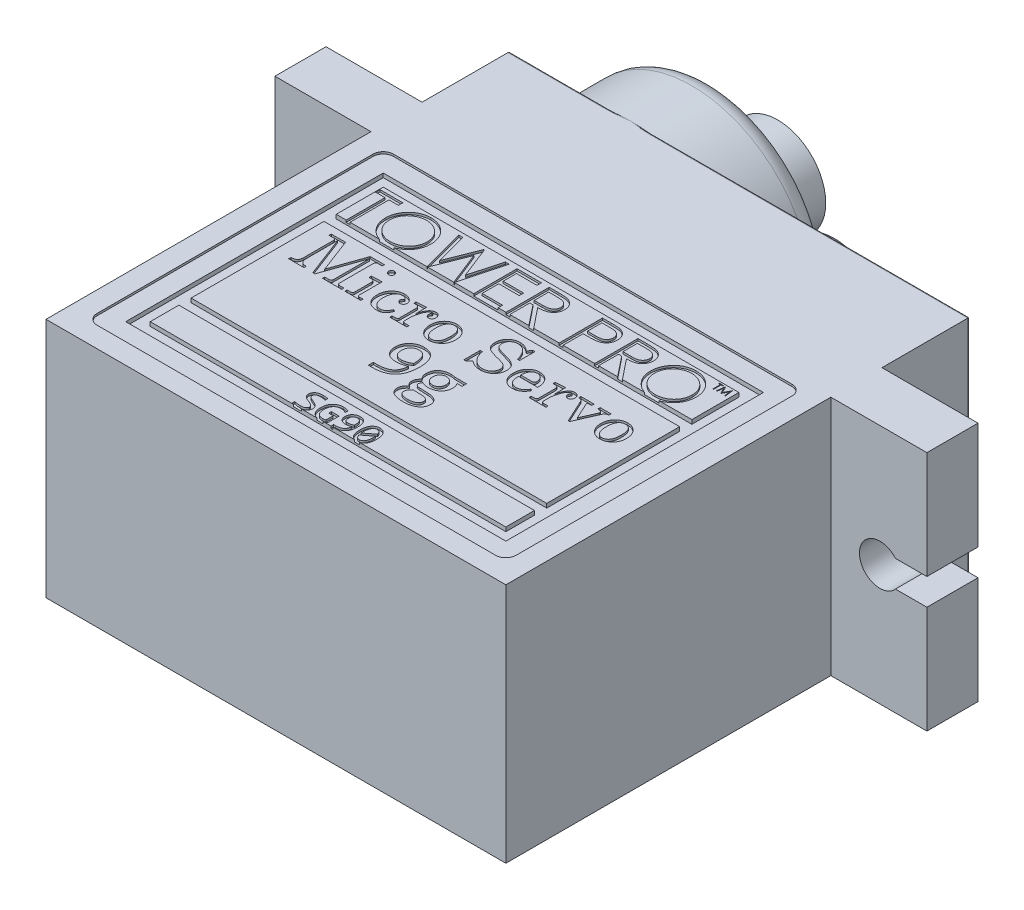
SolidWorks part; units mm, degrees
ref_plane "Front Plane" through (0, 0, 0) normal (0, 0, 1) x (1, 0, 0)
ref_plane "Top Plane" through (0, 0, 0) normal (0, 1, 0) x (1, 0, 0)
ref_plane "Right Plane" through (0, 0, 0) normal (1, 0, 0) x (0, 0, -1)
sketch "Sketch1" plane through (0, 0, 0) normal (0, 1, 0) x (1, 0, 0)
  line L1 (-11.25, -11.35) -> (11.25, -11.35)
  line L2 (-11.25, -11.35) -> (-11.25, 11.35)
  line L3 (-11.25, 11.35) -> (11.25, 11.35)
  line L4 (11.25, -11.35) -> (11.25, 11.35)
  line L5 (-11.25, -11.35) -> (11.25, 11.35) construction
  line L6 (-11.25, 11.35) -> (11.25, -11.35) construction
  point P0 (0, 0)
  dimension "D1" = 22.5
  dimension "D2" = 22.7
extrude "Boss-Extrude1" add sketch "Sketch1" along normal mid plane 11.8
sketch "Sketch2" plane through (11.25, 0, 0) normal (1, 0, 0) x (0, 0, -1)
  line L0 (-11.35, -5.9) -> (11.35, -5.9) construction
  line L1 (7.05, -5.9) -> (4.55, -5.9)
  line L2 (7.05, -5.9) -> (7.05, 5.9)
  line L3 (7.05, 5.9) -> (4.55, 5.9)
  line L4 (4.55, -5.9) -> (4.55, 5.9)
  line L5 (-11.35, 5.9) -> (11.35, 5.9) construction
  line L6 (-11.35, 5.9) -> (-11.35, -5.9) construction
  dimension "D1" = 2.5
  dimension "D2" = 15.9
extrude "Boss-Extrude2" add sketch "Sketch2" along normal blind 4.7
sketch "Sketch3" plane through (-11.25, 0, 0) normal (-1, 0, 0) x (0, 0, 1)
  line L0 (-11.35, -5.9) -> (11.35, -5.9) construction
  line L1 (-7.05, -5.9) -> (-4.55, -5.9)
  line L2 (-7.05, -5.9) -> (-7.05, 5.9)
  line L3 (-7.05, 5.9) -> (-4.55, 5.9)
  line L4 (-4.55, -5.9) -> (-4.55, 5.9)
  line L5 (-11.35, 5.9) -> (11.35, 5.9) construction
  line L6 (11.35, 5.9) -> (11.35, -5.9) construction
  dimension "D1" = 15.9
  dimension "D2" = 2.5
extrude "Boss-Extrude3" add sketch "Sketch3" along normal blind 4.7
sketch "Sketch4" plane through (0, 0, -11.35) normal (0, 0, -1) x (-1, 0, 0)
  line L0 (11.25, 5.9) -> (11.25, -5.9) construction
  line L1 (-11.25, -5.9) -> (11.25, -5.9) construction
  arc A0 (-0.0667, -2.3387) -> (-0.0667, 2.3387) centre (5.35, 0) ccw
  arc A1 (-0.0667, 2.3387) -> (-0.0667, -2.3387) centre (-0.95, 0) ccw
  dimension "D1" = 11.8
  dimension "D4" = 5
  dimension "D2" = 5.9
  dimension "D3" = 5.9
  dimension "D5" = 6.3
extrude "Boss-Extrude5" add sketch "Sketch4" along normal blind 4
sketch "Sketch7" plane through (0, 0, -7.05) normal (0, 0, -1) x (-1, 0, 0)
  line L0 (-15.95, -5.9) -> (-15.95, 5.9) construction
  line L1 (-14.4099, 0.65) -> (-15.95, 0.65)
  line L2 (-15.95, 0.65) -> (-15.95, -0.65)
  line L3 (-15.95, -0.65) -> (-14.4099, -0.65)
  line L4 (14.4099, 0.65) -> (15.95, 0.65)
  line L5 (15.95, 5.9) -> (15.95, -5.9) construction
  line L6 (15.95, 0.65) -> (15.95, -0.65)
  line L7 (15.95, -0.65) -> (14.4099, -0.65)
  line L10 (-15.95, 5.9) -> (-11.25, 5.9) construction
  line L11 (15.95, 5.9) -> (11.25, 5.9) construction
  line L12 (12.1344, 0) -> (15.1656, 0) construction
  line L13 (-12.15, 0) -> (-15.15, 0) construction
  arc A0 (-14.4099, -0.65) -> (-14.4099, 0.65) centre (-13.65, 0) ccw
  arc A1 (14.4099, 0.65) -> (14.4099, -0.65) centre (13.65, 0) ccw
  dimension "D3" = 2
  dimension "D4" = 2
  dimension "D1" = 5.9
  dimension "D2" = 5.9
  dimension "D5" = 2.3
  dimension "D6" = 2.3
  dimension "D7" = 0.65
  dimension "D8" = 0.65
  dimension "D9" = 3
  dimension "D10" = 0.65
  dimension "D11" = 0.65
extrude "Cut-Extrude6" cut sketch "Sketch7" against normal through all
sketch "Sketch11" plane through (0, 5.9, 0) normal (0, 1, 0) x (1, 0, 0)
  line L1 (-9.75, -10.35) -> (9.75, -10.35)
  line L2 (-10.25, -9.85) -> (-10.25, 3.65)
  line L3 (-9.75, 4.15) -> (9.75, 4.15)
  line L4 (10.25, -9.85) -> (10.25, 3.65)
  line L5 (-10.25, -10.35) -> (10.25, 4.15) construction
  line L6 (-10.25, 4.15) -> (10.25, -10.35) construction
  line L7 (-11.25, -11.35) -> (11.25, -11.35) construction
  line L8 (11.25, -11.35) -> (11.25, 4.55) construction
  line L9 (-11.25, 4.55) -> (-11.25, -11.35) construction
  arc A0 (-9.75, -10.35) -> (-10.25, -9.85) centre (-9.75, -9.85) cw
  arc A1 (9.75, -10.35) -> (10.25, -9.85) centre (9.75, -9.85) ccw
  arc A2 (9.75, 4.15) -> (10.25, 3.65) centre (9.75, 3.65) cw
  arc A3 (-10.25, 3.65) -> (-9.75, 4.15) centre (-9.75, 3.65) cw
  point P0 (0, -3.1)
  dimension "D1" = 0.5
  dimension "D2" = 13.5
  dimension "D3" = 1
  dimension "D4" = 1
  dimension "D5" = 1
extrude "Cut-Extrude7" cut sketch "Sketch11" against normal blind 0.1
fillet "Fillet8" radius 0.1 7 edges at (-11.25, 2.95, -11.35) (-11.25, -2.95, -11.35) (-8.3, -5.9, -11.35) (11.25, 0, -11.35) (2.95, -5.9, -11.35) (2.95, 5.9, -11.35) (-8.3, 5.9, -11.35)
sketch "Sketch18" plane through (0, 5.8, 0) normal (0, 1, 0) x (1, 0, 0)
  line L0 (-8.7, 0.3) -> (-8.7, 2.6)
  line L1 (8.7, -0.3) -> (8.7, -6.8)
  line L2 (8.7, -7.4) -> (8.7, -8.8)
  line L3 (-8.7, -6.8) -> (-8.7, -0.3)
  line L5 (9.75, 4.15) -> (-9.75, 4.15) construction
  line L6 (-10.25, 3.65) -> (-10.25, -9.85) construction
  line L7 (10.25, -9.85) -> (10.25, 3.65) construction
  line L10 (-9.3, 3.2) -> (9.3, 3.2)
  line L11 (9.3, 3.2) -> (9.3, -9.4)
  line L12 (9.3, -9.4) -> (-9.3, -9.4)
  line L13 (-9.3, -9.4) -> (-9.3, 3.2)
  line L14 (-8.7, -0.3) -> (8.7, -0.3)
  line L15 (-8.7, -7.4) -> (8.7, -7.4)
  line L16 (-8.7, 2.6) -> (8.7, 2.6)
  line L17 (8.7, 2.6) -> (8.7, 0.3)
  line L18 (8.7, -8.8) -> (-8.7, -8.8)
  line L19 (-8.7, -8.8) -> (-8.7, -7.4)
  line L20 (-8.7, 0.3) -> (8.7, 0.3)
  line L21 (-8.7, -6.8) -> (8.7, -6.8)
  dimension "D1" = 12.6
  dimension "D2" = 17.4
  dimension "D3" = 17.4
  dimension "D4" = 17.4
  dimension "D5" = 18.6
  dimension "D6" = 17.4
  dimension "D7" = 17.4
  dimension "D8" = 17.4
  dimension "D9" = 1.4
  dimension "D10" = 0.95
  dimension "D11" = 0.6
  dimension "D12" = 0.6
  dimension "D13" = 0.95
  dimension "D14" = 0.95
  dimension "D15" = 0.6
  dimension "D16" = 0.6
extrude "Cut-Extrude16" cut sketch "Sketch18" against normal blind 0.2
sketch "Sketch19" plane through (0, 5.8, 0) normal (0, 1, 0) x (1, 0, 0)
  line L0 (7.7319, 2.119) -> (8.6448, 2.119) construction
  line L1 (8.7, 2.6) -> (-8.7, 2.6) construction
  line L3 (-8.7, -2.748) -> (8.6448, -2.748) construction
  line L4 (-8.7, -0.3) -> (-8.7, -6.8) construction
  line L5 (-8.7, -5.3084) -> (8.7, -5.3084) construction
  line L6 (8.7, -6.8) -> (8.7, -0.3) construction
  line L7 (8.7, -0.3) -> (-8.7, -0.3) construction
  line L8 (-8.7, -6.8) -> (8.7, -6.8) construction
  text T0 "TOWER PRO" font "Century Gothic" height in points 8
  text T1 "TM" font "Century Gothic" height 0.4
  text T2 "Micro Servo" font "Century" height in points 8
  text T3 "9g" font "Consolas" height in points 8
  text T4 "SG90" font "Consolas" height 1.096
  dimension "D1" = 0.9129
  dimension "D2" = 0.481
  dimension "D3" = 2.448
  dimension "D4" = 1.4916
extrude "Cut-Extrude17" cut sketch "Sketch19" against normal blind 0.1
fillet "Fillet9" radius 1 2 edges at (3.45, 0, -15.35) (-11.25, 0, -15.35)
sketch "Sketch20" plane through (0, 0, -15.35) normal (0, 0, -1) x (-1, 0, 0)
  circle A0 centre (5.35, 0) radius 2.35
  dimension "D1" = 4.7
extrude "Boss-Extrude6" add sketch "Sketch20" along normal blind 3.2
sketch "Sketch21" plane through (0, 0, -18.55) normal (0, 0, -1) x (-1, 0, 0)
  circle A0 centre (5.35, 0) radius 1
  dimension "D1" = 2
extrude "Cut-Extrude18" cut sketch "Sketch21" against normal blind 0.225
sketch "Sketch23" plane through (0, 0, -18.325) normal (0, 0, -1) x (-1, 0, 0)
  line L0 (5.35, -0.82) -> (5.35, 0.82) construction
  line L1 (5.17, -0.82) -> (5.17, -0.18)
  line L2 (5.53, -0.82) -> (5.53, -0.18)
  line L3 (6.17, 0) -> (4.53, 0) construction
  line L4 (6.17, -0.18) -> (5.53, -0.18)
  line L5 (6.17, 0.18) -> (5.53, 0.18)
  line L6 (5.17, 0.18) -> (4.53, 0.18)
  line L7 (5.53, 0.18) -> (5.53, 0.82)
  line L8 (5.17, -0.18) -> (4.53, -0.18)
  line L9 (5.17, 0.18) -> (5.17, 0.82)
  arc A0 (5.17, -0.82) -> (5.53, -0.82) centre (5.35, -0.82) ccw
  arc A1 (5.53, 0.82) -> (5.17, 0.82) centre (5.35, 0.82) ccw
  arc A2 (6.17, -0.18) -> (6.17, 0.18) centre (6.17, 0) ccw
  arc A3 (4.53, 0.18) -> (4.53, -0.18) centre (4.53, 0) ccw
  circle A4 centre (5.35, 0) radius 1 construction
  point P2 (5.35, 0)
  point P9 (5.35, 0)
  dimension "D1" = 0.18
  dimension "D2" = 0.18
  dimension "D3" = 0.18
  dimension "D4" = 0.18
  dimension "D5" = 0.64
  dimension "D6" = 0.64
  dimension "D7" = 0.64
  dimension "D8" = 0.64
  dimension "D9" = 0.64
  dimension "D10" = 0.64
  dimension "D11" = 0.64
  dimension "D12" = 0.36
extrude "Cut-Extrude19" cut sketch "Sketch23" against normal blind 1
